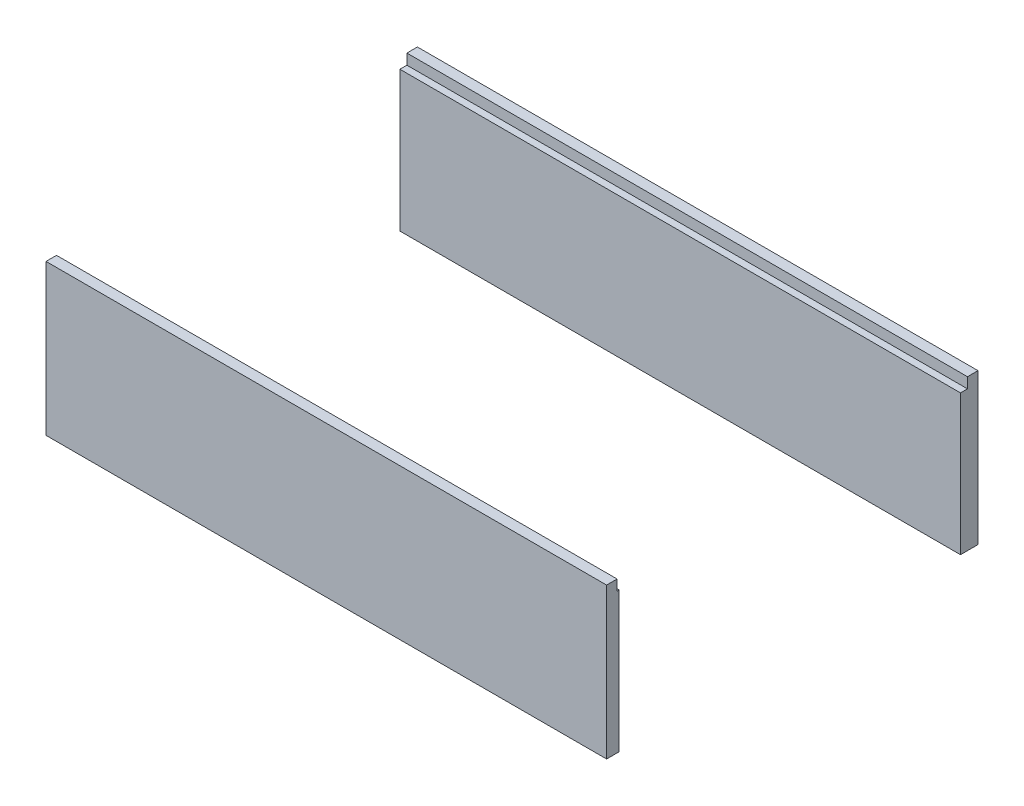
SolidWorks part; units mm, degrees
ref_plane "Front Plane" through (0, 0, 0) normal (0, 0, 1) x (1, 0, 0)
ref_plane "Top Plane" through (0, 0, 0) normal (0, 1, 0) x (1, 0, 0)
ref_plane "Right Plane" through (0, 0, 0) normal (1, 0, 0) x (0, 0, -1)
sketch "Sketch3" plane through (0, 0, 0) normal (0, 1, 0) x (1, 0, 0)
  line L1 (-39.8113, 2.7358) -> (40.1887, 2.7358)
  line L2 (-39.8113, 2.7358) -> (-39.8113, 0.2358)
  line L3 (-39.8113, 0.2358) -> (40.1887, 0.2358)
  line L4 (40.1887, 2.7358) -> (40.1887, 0.2358)
  line L5 (-39.8113, -50.2642) -> (40.1887, -50.2642)
  line L6 (-39.8113, -50.2642) -> (-39.8113, -48.4642)
  line L7 (-39.8113, -48.4642) -> (40.1887, -48.4642)
  line L8 (40.1887, -50.2642) -> (40.1887, -48.4642)
  dimension "D1" = 80
  dimension "D2" = 2.5
  dimension "D3" = 1.8
  dimension "D4" = 53
extrude "Boss-Extrude1" add sketch "Sketch3" along normal blind 21.5
sketch "Sketch4" plane through (0, 21.5, 0) normal (0, 1, 0) x (1, 0, 0)
  line L1 (-39.8113, -48.4642) -> (40.1887, -48.4642)
  line L2 (-39.8113, -48.4642) -> (-39.8113, -48.7642)
  line L3 (-39.8113, -48.7642) -> (40.1887, -48.7642)
  line L4 (40.1887, -48.4642) -> (40.1887, -48.7642)
  dimension "D1" = 0.3
  dimension "D2" = 80
extrude "Cut-Extrude1" cut sketch "Sketch4" against normal blind 1.5
sketch "Sketch5" plane through (0, 21.5, 0) normal (0, 1, 0) x (1, 0, 0)
  line L1 (-39.8113, 0.2358) -> (40.1887, 0.2358)
  line L2 (-39.8113, 0.2358) -> (-39.8113, 1.2358)
  line L3 (-39.8113, 1.2358) -> (40.1887, 1.2358)
  line L4 (40.1887, 0.2358) -> (40.1887, 1.2358)
  dimension "D1" = 80
  dimension "D2" = 1
extrude "Cut-Extrude2" cut sketch "Sketch5" against normal blind 1.5
